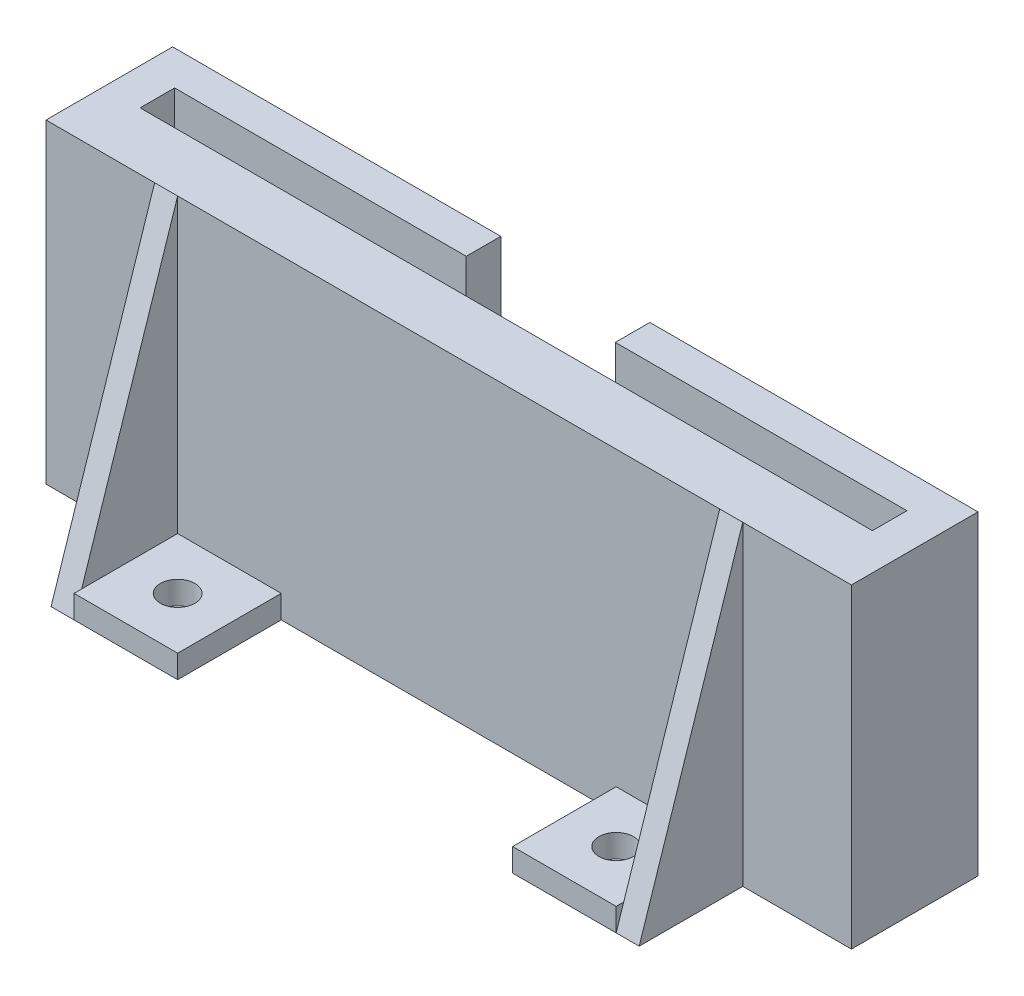
SolidWorks part; units mm, degrees
ref_plane "Front Plane" through (0, 0, 0) normal (0, 0, 1) x (1, 0, 0)
ref_plane "Top Plane" through (0, 0, 0) normal (0, 1, 0) x (1, 0, 0)
ref_plane "Right Plane" through (0, 0, 0) normal (1, 0, 0) x (0, 0, -1)
sketch "Sketch1" plane through (0, 0, 0) normal (0, 1, 0) x (1, 0, 0)
  line L1 (34.9885, 5.5) -> (-34.9885, 5.5)
  line L2 (34.9885, 5.5) -> (34.9885, -5.5)
  line L3 (34.9885, -5.5) -> (-34.9885, -5.5)
  line L4 (-34.9885, 5.5) -> (-34.9885, -5.5)
  line L5 (34.9885, 5.5) -> (-34.9885, -5.5) construction
  line L6 (34.9885, -5.5) -> (-34.9885, 5.5) construction
  line L7 (-34.9885, 2.5) -> (-6.477, 2.5)
  line L8 (-34.9885, 2.5) -> (-34.9885, 5.5)
  line L9 (-34.9885, 5.5) -> (-6.477, 5.5)
  line L10 (-6.477, 2.5) -> (-6.477, 5.5)
  line L15 (34.9885, 5.5) -> (6.477, 5.5)
  line L16 (34.9885, 5.5) -> (34.9885, 2.5)
  line L17 (34.9885, 2.5) -> (6.477, 2.5)
  line L18 (6.477, 5.5) -> (6.477, 2.5)
  line L23 (-34.9885, -5.5) -> (34.9885, -5.5)
  line L24 (-34.9885, -5.5) -> (-34.9885, -0.5)
  line L25 (-34.9885, -0.5) -> (34.9885, -0.5)
  line L26 (34.9885, -5.5) -> (34.9885, -0.5)
  line L27 (-31.8135, 2.5) -> (-34.9885, 2.5)
  line L28 (-31.8135, 2.5) -> (-31.8135, -0.5)
  line L29 (-31.8135, -0.5) -> (-34.9885, -0.5)
  line L30 (-34.9885, 2.5) -> (-34.9885, -0.5)
  line L31 (34.9885, 2.5) -> (31.8135, 2.5)
  line L32 (34.9885, 2.5) -> (34.9885, -0.5)
  line L33 (34.9885, -0.5) -> (31.8135, -0.5)
  line L34 (31.8135, 2.5) -> (31.8135, -0.5)
  point P0 (0, 0)
  dimension "D1" = 69.977
  dimension "D2" = 12.954
  dimension "D3" = 3
  dimension "D4" = 5
  dimension "D5" = 3
  dimension "D6" = 3.175
  dimension "D7" = 3.175
extrude "Boss-Extrude1" add sketch "Sketch1" along normal blind 2 contours L1 L18 L17 L2 | L4 L25 L2 L17 L18 L1 L10 L7 | L25 L4 L3 L2 | L7 L10 L1 L4 | L28 L7 L4 L25 | L17 L34 L25 L2 region at (20.7328, 0, -4) region at (0, 0, -1.5075) region at (33.401, 0, -1) region at (-20.7327, 0, -4) region at (0, 0, 3) region at (-33.401, 0, -1)
extrude "Boss-Extrude2" add sketch "Sketch1<4>" along normal blind 25.4 from surface contours L25 L4 L3 L2 | L7 L10 L1 L4 | L1 L18 L17 L2 | L28 L7 L4 L25 | L17 L34 L25 L2 region at (20.7328, 0, -4) region at (33.401, 0, -1) region at (-20.7327, 0, -4) region at (0, 0, 3) region at (-33.401, 0, -1) starting at face at (0, 2, 0)
sketch "Sketch1<4>" plane through (0, 0, 0) normal (0, 1, 0) x (1, 0, 0) same geometry as "Sketch1"
sketch "Sketch3" plane through (0, 0, 0) normal (0, -1, 0) x (1, 0, 0)
  line L0 (-34.9885, 5.5) -> (34.9885, 5.5) construction
  line L1 (-23.55, 5.5) -> (-14.55, 5.5)
  line L2 (-23.55, 5.5) -> (-23.55, 14.5)
  line L3 (-23.55, 14.5) -> (-14.55, 14.5)
  line L4 (-14.55, 5.5) -> (-14.55, 14.5)
  line L5 (-19.05, 10) -> (19.05, 10) construction
  line L6 (14.55, 5.5) -> (23.55, 5.5)
  line L7 (14.55, 5.5) -> (14.55, 14.5)
  line L8 (14.55, 14.5) -> (23.55, 14.5)
  line L9 (23.55, 5.5) -> (23.55, 14.5)
  line L10 (-19.05, 10) -> (-19.05, 14.5) construction
  line L11 (19.05, 10) -> (19.05, 14.5) construction
  line L12 (0, 10) -> (0, 0) construction
  circle A0 centre (-19.05, 10) radius 1.5
  circle A1 centre (19.05, 10) radius 1.5
  point P19 (-52.9487, 19.3279)
  point P20 (-14.55, 10)
  point P21 (-44.45, 12.0595)
  dimension "D1" = 3
  dimension "D2" = 9
  dimension "D3" = 38.1
extrude "Boss-Extrude3" add sketch "Sketch3" against normal blind 2
sketch "Sketch4" plane through (-23.55, 0, 0) normal (-1, 0, 0) x (0, 0, 1)
  line L0 (14.5, 0) -> (5.5, 27.4)
  line L1 (5.5, 27.4) -> (5.5, 0)
  line L2 (5.5, 0) -> (14.5, 0)
  point P4 (0, 0)
  point P7 (0, 0)
  point P8 (14.5, 0)
extrude "Boss-Extrude4" add sketch "Sketch4" along normal blind 2
extrude "Boss-Extrude5" add sketch "Sketch4<2>" against normal blind 2 from surface starting at face at (23.55, 1, 10)
sketch "Sketch4<2>" plane through (-23.55, 0, 0) normal (-1, 0, 0) x (0, 0, 1) same geometry as "Sketch4"
